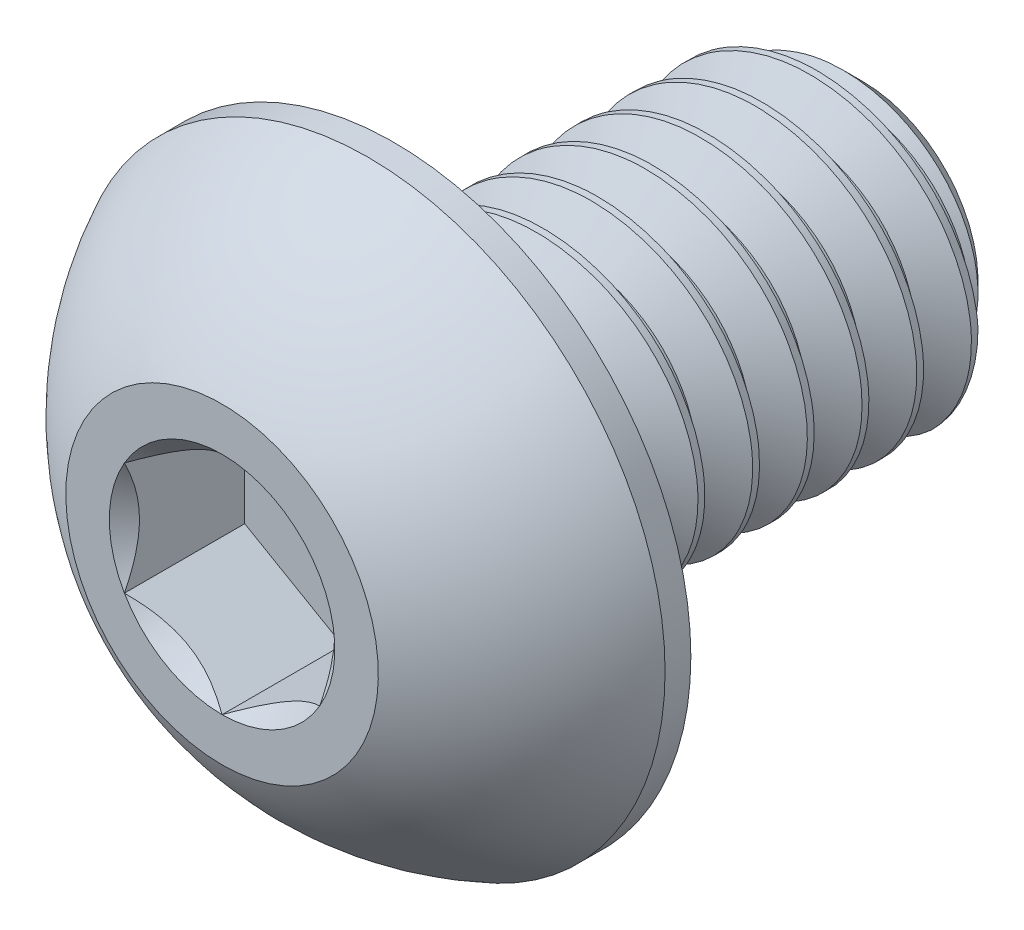
SolidWorks part; units mm, degrees
ref_plane "Front" through (0, 0, 0) normal (0, 0, 1) x (1, 0, 0)
ref_plane "Top" through (0, 0, 0) normal (0, 1, 0) x (1, 0, 0)
ref_plane "Right" through (0, 0, 0) normal (1, 0, 0) x (0, 0, -1)
sketch "Sketch1" plane through (0, 0, 0) normal (1, 0, 0) x (0, 0, -1)
  line L2 (2.2, 2) -> (8.2, 2)
  line L3 (8.2, 2) -> (8.2, 0)
  line L4 (8.2, 0) -> (2.2, 0)
  line L6 (1.87, 3.8) -> (2.2, 3.8) construction
  line L7 (8.2, 2) -> (8.2, -2) construction
  line L8 (0, 0) -> (2.2, 0) construction
  line L9 (2.2, 3.8) -> (2.2, -3.8) construction
  line L11 (2.2, 2) -> (2.2, 0)
  line L13 (0, 1.25) -> (0, -1.25) construction
  line L14 (0, 1.25) -> (0, 2) construction
  arc A3 (0, 2) -> (1.87, 3.8) centre (3.7264, 0) cw construction
  dimension "D1" = 0.33
revolve "Revolve1" add sketch "Sketch1" angle 360 mid plane about L4
sketch "Sketch3" plane through (0, 0, -8.2) normal (0, 0, -1) x (-1, 0, 0)
  circle A0 centre (0, 0) radius 2
curve "Helix/Spiral1" pitch 0.7 height 6.7 radius 2 centre (0, 0, -8.2) axis (0, 0, 1) start towards (0, 1, 0)
sketch "Sketch2" plane through (0, 0, 0) normal (1, 0, 0) x (0, 0, -1)
  line L0 (8.2, 2) -> (8.8125, 2)
  line L1 (8.8125, 2) -> (8.55, 1.5453)
  line L2 (8.55, 1.5453) -> (8.4625, 1.5453)
  line L3 (8.4625, 1.5453) -> (8.2, 2)
  line L4 (8.3312, 1.7727) -> (8.6812, 1.7727) construction
  dimension "D1" = 60
  dimension "D2" = 0.0875
  dimension "D3" = 0.35
chamfer "Chamfer1" distance 0.525 angle 45 1 edges at (0, 2, -8.2)
sweep "Cut-Sweep1" cut profiles "Sketch2" path "Helix/Spiral1" align with end faces yes
sketch "Sketch7" plane through (0, 0, 0) normal (1, 0, 0) x (0, 0, -1)
  line L6 (1.87, 3.8) -> (2.2, 3.8) construction
  line L8 (0, 0) -> (2.2, 0) construction
  line L11 (2.2, 3.8) -> (2.2, -3.8) construction
  line L12 (1.87, 3.8) -> (2.2, 3.8)
  line L13 (0, 0) -> (2.2, 0)
  line L14 (0, 1.25) -> (0, -1.25) construction
  line L15 (2.2, 3.8) -> (2.2, 0)
  line L16 (0, 2) -> (0, 0)
  arc A2 (1.87, 3.8) -> (0, 2) centre (3.7264, 0) ccw construction
  arc A3 (1.87, 3.8) -> (0, 2) centre (3.7264, 0) ccw
revolve "Revolve2" add sketch "Sketch7" angle 360 mid plane about L13
sketch "Sketch5" plane through (0, 0, 0) normal (0, 0, 1) x (1, 0, 0)
  line L1 (1.25, -0.7217) -> (1.25, 0.7217)
  line L2 (1.25, 0.7217) -> (0, 1.4434)
  line L3 (0, 1.4434) -> (-1.25, 0.7217)
  line L4 (-1.25, 0.7217) -> (-1.25, -0.7217)
  line L5 (-1.25, -0.7217) -> (0, -1.4434)
  line L6 (0, -1.4434) -> (1.25, -0.7217)
  circle A0 centre (0, 0) radius 1.25 construction
extrude "Cut-Extrude2" cut sketch "Sketch5" against normal blind 1.54
sketch "Sketch6" plane through (0, 0, 0) normal (0, 0, 1) x (1, 0, 0)
  circle A0 centre (0, 0) radius 1.4434
extrude "Cut-Extrude3" cut sketch "Sketch6" against normal blind 1.54 draft 45
sketch "Sketch9" [suppressed] plane through (0, 0, -2.2) normal (0, 0, 1) x (1, 0, 0)
  circle A2 centre (0, 0) radius 2
extrude "Boss-Extrude2" [suppressed] add sketch "Sketch9" against normal offset from surface (5 mm away) 28.575 up to face at (0, 1.475, -8.2)
sketch "Sketch10" plane through (0, 0, 0) normal (1, 0, 0) x (0, 0, -1)
  line L0 (8.2, 2) -> (8.2, -2) construction
  point P0 (7.15, -2)
  dimension "D1" = 1.05
equation "\"D3@Helix/Spiral1\" = \"Lg@Sketch1\" + \"D4@Helix/Spiral1\""
equation "\"D2@Sketch2\" = \"D4@Helix/Spiral1\" * .125"
equation "\"D3@Sketch2\" = \"D4@Helix/Spiral1\" * .5"
equation "\"D1@Chamfer1\" = \"D4@Helix/Spiral1\" * .75"
equation "\"D1@Cut-Extrude2\" = \"Head Ht@Sketch1\" * .7"
equation "\"D1@Sketch1\" = \"Head Ht@Sketch1\" * .15"
equation "\"D1@Sketch10\" = \"D4@Helix/Spiral1\" * 1.5"
equation "\"D1@Cut-Extrude3\" = \"D1@Cut-Extrude2\""
